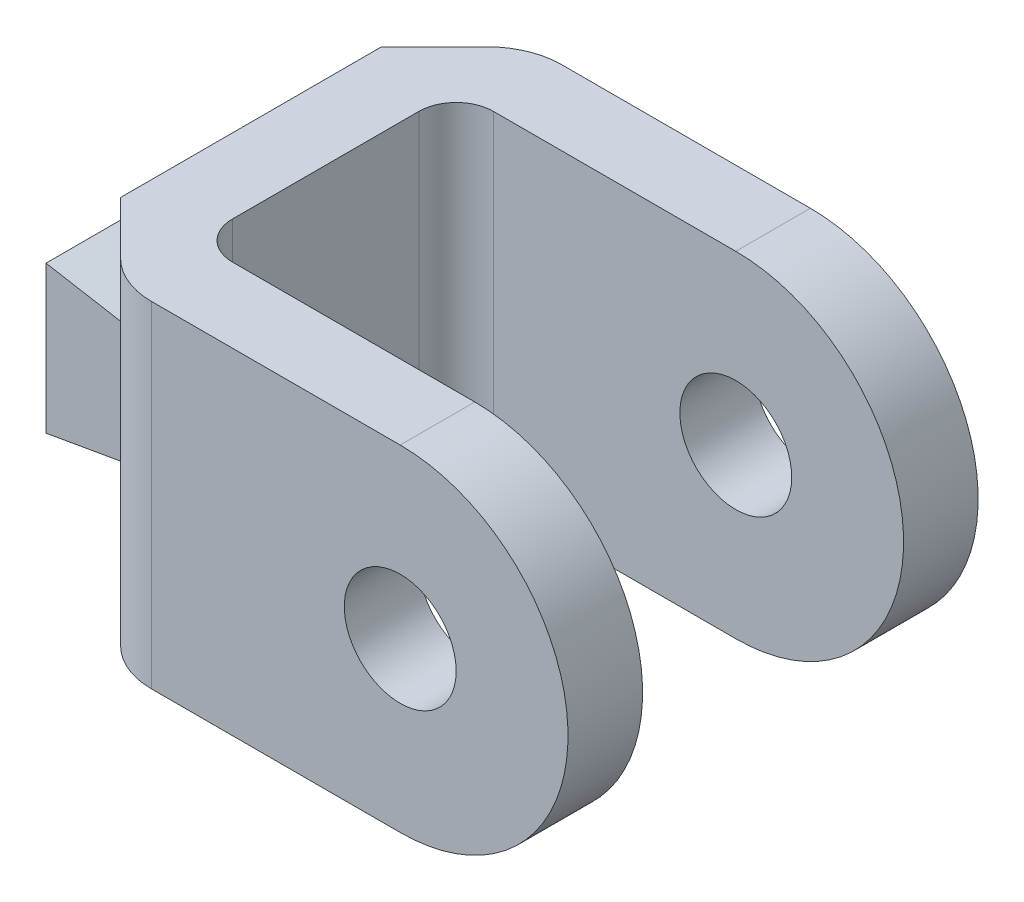
SolidWorks part; units mm, degrees
ref_plane "Front Plane" through (0, 0, 0) normal (0, 0, 1) x (1, 0, 0)
ref_plane "Top Plane" through (0, 0, 0) normal (0, 1, 0) x (1, 0, 0)
ref_plane "Right Plane" through (0, 0, 0) normal (1, 0, 0) x (0, 0, -1)
sketch "Sketch1" plane through (0, 0, 0) normal (0, 0, 1) x (1, 0, 0)
  line L0 (-7.1268, 0) -> (0, 0) construction
  line L1 (0, -4.5) -> (0, -1.625) construction
  line L2 (0, -1.625) -> (-2, -1.975)
  line L6 (-2, -1.975) -> (-2, 1.975)
  line L7 (0, 0) -> (-2, 1.975) construction
  line L8 (0, 0) -> (-2, -1.975) construction
  line L9 (0, 1.625) -> (-2, 1.975)
  line L11 (0, 0) -> (6.5352, 0) construction
  line L12 (0, 1.625) -> (0, 4.5)
  line L13 (0, -4.5) -> (2, -4.5)
  line L14 (0, -4.5) -> (0, -1.625)
  line L15 (0, 4.5) -> (2, 4.5)
  line L16 (2, -4.5) -> (2, 4.5)
  line L17 (0, 1.625) -> (0, 4.499) construction
  point P5 (0, 0)
  point P10 (0, 1.625)
  point P12 (0, -1.625)
  point P16 (-2, 0)
  dimension "D1" = 2
  dimension "D2" = 3.95
  dimension "D3" = 9
  dimension "D4" = 4.5
  dimension "D5" = 3.25
extrude "Boss-Extrude2" add sketch "Sketch1" along normal blind 7
sketch "Sketch2" plane through (0, 0, 0) normal (0, 0, 1) x (1, 0, 0)
  line L1 (0, 4.5) -> (9.5, 4.5)
  line L2 (0, 4.5) -> (0, -4.5)
  line L3 (0, -4.5) -> (9.5, -4.5)
  arc A0 (9.5, -4.5) -> (9.5, 4.5) centre (9.5, 0) ccw
  circle A1 centre (9.5, 0) radius 1.5
  circle A2 centre (9.5, 0) radius 6.5 construction
  point P1 (14, 0)
  point P11 (3, 0)
  dimension "D3" = 3
  dimension "D2" = 13
  dimension "D1" = 14
extrude "Boss-Extrude3" add sketch "Sketch2" against normal blind 2
ref_plane "Plane1" through (0, 4.5, 0) normal (0, 1, 0) x (1, 0, 0)
sketch "Sketch4" plane through (0, 4.5, 0) normal (0, 1, 0) x (1, 0, 0)
  line L0 (2, 0) -> (2, 2.9724) construction
  line L1 (9.5, 2) -> (0, 2) construction
  line L2 (0, 0) -> (2, 2)
  line L3 (2, 2) -> (0, 2)
  line L4 (0, 0) -> (0, 2)
  point P0 (2, 0)
  point P4 (2, 2)
extrude "Cut-Extrude3" cut sketch "Sketch4" against normal through all
fillet "Fillet1" radius 1 1 edges at (2, 0, 0)
fillet "Fillet2" radius 2 1 edges at (2, 0, -2)
ref_plane "Plane2" through (0, 0, 3.5) normal (0, 0, 1) x (1, 0, 0)
mirror "Mirror2" about plane through (0, 0, 3.5) normal (0, 0, 1) of "Boss-Extrude2", "Fillet2", "Cut-Extrude3", "Boss-Extrude3"
fillet "Fillet3" radius 1 1 edges at (2, 0, 7)
